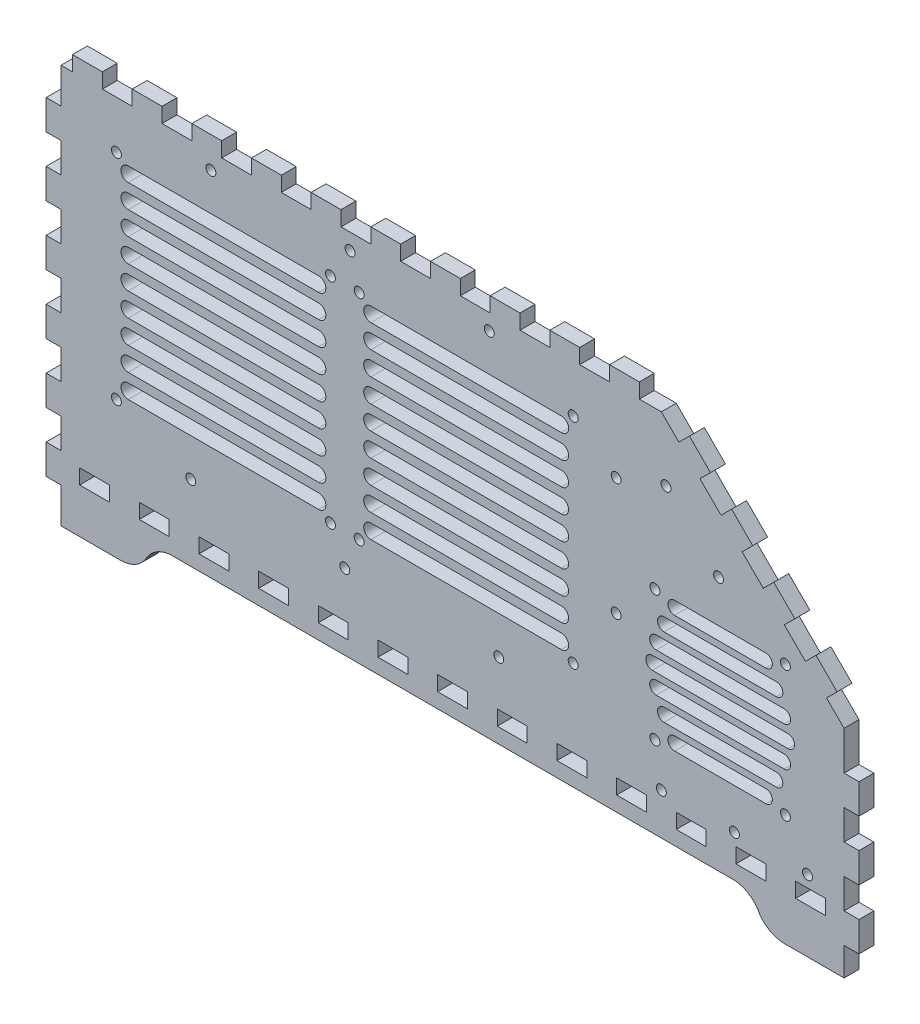
SolidWorks part; units mm, degrees
ref_plane "Front Plane" through (0, 0, 0) normal (0, 0, 1) x (1, 0, 0)
ref_plane "Top Plane" through (0, 0, 0) normal (0, 1, 0) x (1, 0, 0)
ref_plane "Right Plane" through (0, 0, 0) normal (1, 0, 0) x (0, 0, -1)
sketch "Model" plane through (0, 0, 0) normal (0, 0, 1) x (1, 0, 0)
  line L4 (28.9553, 40.0032) -> (23.2406, 40.0032)
  line L5 (23.2406, 40.0032) -> (23.2406, 45.7179)
  line L6 (23.2406, 45.7179) -> (34.67, 45.7179)
  line L7 (34.67, 45.7179) -> (34.67, 40.0032)
  line L8 (34.67, 40.0032) -> (28.9553, 40.0032)
  line L9 (51.8156, 40.0032) -> (46.0996, 40.0032)
  line L10 (46.0996, 40.0032) -> (46.0996, 45.7179)
  line L11 (46.0996, 45.7179) -> (57.5303, 45.7179)
  line L12 (57.5303, 45.7179) -> (57.5303, 40.0032)
  line L13 (57.5303, 40.0032) -> (51.8156, 40.0032)
  line L14 (74.6746, 40.0032) -> (68.9599, 40.0032)
  line L15 (68.9599, 40.0032) -> (68.9599, 45.7179)
  line L16 (68.9599, 45.7179) -> (80.3906, 45.7179)
  line L17 (80.3906, 45.7179) -> (80.3906, 40.0032)
  line L18 (80.3906, 40.0032) -> (74.6746, 40.0032)
  line L19 (97.5349, 40.0032) -> (91.8199, 40.0032)
  line L20 (91.8199, 40.0032) -> (91.8199, 45.7179)
  line L21 (91.8199, 45.7179) -> (103.25, 45.7179)
  line L22 (103.25, 45.7179) -> (103.25, 40.0032)
  line L23 (103.25, 40.0032) -> (97.5349, 40.0032)
  line L24 (120.395, 40.0032) -> (114.68, 40.0032)
  line L25 (114.68, 40.0032) -> (114.68, 45.7179)
  line L26 (114.68, 45.7179) -> (126.11, 45.7179)
  line L27 (126.11, 45.7179) -> (126.11, 40.0032)
  line L28 (126.11, 40.0032) -> (120.395, 40.0032)
  line L29 (143.255, 40.0032) -> (137.541, 40.0032)
  line L30 (137.541, 40.0032) -> (137.541, 45.7179)
  line L31 (137.541, 45.7179) -> (148.97, 45.7179)
  line L32 (148.97, 45.7179) -> (148.97, 40.0032)
  line L33 (148.97, 40.0032) -> (143.255, 40.0032)
  line L34 (166.116, 40.0032) -> (160.4, 40.0032)
  line L35 (160.4, 40.0032) -> (160.4, 45.7179)
  line L36 (160.4, 45.7179) -> (171.83, 45.7179)
  line L37 (171.83, 45.7179) -> (171.83, 40.0032)
  line L38 (171.83, 40.0032) -> (166.116, 40.0032)
  line L39 (188.975, 40.0032) -> (183.26, 40.0032)
  line L40 (183.26, 40.0032) -> (183.26, 45.7179)
  line L41 (183.26, 45.7179) -> (194.691, 45.7179)
  line L42 (194.691, 45.7179) -> (194.691, 40.0032)
  line L43 (194.691, 40.0032) -> (188.975, 40.0032)
  line L44 (211.835, 40.0032) -> (206.12, 40.0032)
  line L45 (206.12, 40.0032) -> (206.12, 45.7179)
  line L46 (206.12, 45.7179) -> (217.55, 45.7179)
  line L47 (217.55, 45.7179) -> (217.55, 40.0032)
  line L48 (217.55, 40.0032) -> (211.835, 40.0032)
  line L49 (234.695, 40.0032) -> (228.98, 40.0032)
  line L50 (228.98, 40.0032) -> (228.98, 45.7179)
  line L51 (228.98, 45.7179) -> (240.41, 45.7179)
  line L52 (240.41, 45.7179) -> (240.41, 40.0032)
  line L53 (240.41, 40.0032) -> (234.695, 40.0032)
  line L54 (257.555, 40.0032) -> (251.841, 40.0032)
  line L55 (251.841, 40.0032) -> (251.841, 45.7179)
  line L56 (251.841, 45.7179) -> (263.27, 45.7179)
  line L57 (263.27, 45.7179) -> (263.27, 40.0032)
  line L58 (263.27, 40.0032) -> (257.555, 40.0032)
  line L59 (280.416, 40.0032) -> (274.7, 40.0032)
  line L60 (274.7, 40.0032) -> (274.7, 45.7179)
  line L61 (274.7, 45.7179) -> (286.13, 45.7179)
  line L62 (286.13, 45.7179) -> (286.13, 40.0032)
  line L63 (286.13, 40.0032) -> (280.416, 40.0032)
  line L64 (303.275, 40.0032) -> (297.56, 40.0032)
  line L65 (297.56, 40.0032) -> (297.56, 45.7179)
  line L66 (297.56, 45.7179) -> (308.991, 45.7179)
  line L67 (308.991, 45.7179) -> (308.991, 40.0032)
  line L68 (308.991, 40.0032) -> (303.275, 40.0032)
  line L69 (16.1148, 22.8575) -> (38.9749, 22.8575)
  line L70 (38.9749, 22.8575) -> (39.3485, 22.8575)
  line L71 (39.3485, 22.8575) -> (40.4689, 22.9567)
  line L72 (40.4689, 22.9567) -> (41.9322, 23.2475)
  line L73 (41.9322, 23.2475) -> (43.3447, 23.7271)
  line L74 (43.3447, 23.7271) -> (44.366, 24.2025)
  line L75 (44.366, 24.2025) -> (44.6899, 24.3885)
  line L76 (44.6899, 24.3885) -> (44.8511, 24.4822)
  line L77 (44.8511, 24.4822) -> (45.3263, 24.7854)
  line L78 (45.3263, 24.7854) -> (45.9341, 25.2222)
  line L79 (45.9341, 25.2222) -> (46.5116, 25.6963)
  line L80 (46.5116, 25.6963) -> (47.056, 26.2062)
  line L81 (47.056, 26.2062) -> (47.5657, 26.7505)
  line L82 (47.5657, 26.7505) -> (48.0399, 27.3279)
  line L83 (48.0399, 27.3279) -> (48.4766, 27.9356)
  line L84 (48.4766, 27.9356) -> (48.7796, 28.411)
  line L85 (48.7796, 28.411) -> (48.8735, 28.5722)
  line L86 (48.8735, 28.5722) -> (48.9673, 28.7348)
  line L87 (48.9673, 28.7348) -> (49.2689, 29.2103)
  line L88 (49.2689, 29.2103) -> (49.7057, 29.818)
  line L89 (49.7057, 29.818) -> (50.1798, 30.3954)
  line L90 (50.1798, 30.3954) -> (50.6899, 30.9397)
  line L91 (50.6899, 30.9397) -> (51.2339, 31.4496)
  line L92 (51.2339, 31.4496) -> (51.8114, 31.9236)
  line L93 (51.8114, 31.9236) -> (52.4192, 32.3605)
  line L94 (52.4192, 32.3605) -> (52.8948, 32.6622)
  line L95 (52.8948, 32.6622) -> (53.0571, 32.756)
  line L96 (53.0571, 32.756) -> (53.3799, 32.9434)
  line L97 (53.3799, 32.9434) -> (54.4008, 33.4188)
  line L98 (54.4008, 33.4188) -> (55.8133, 33.8983)
  line L99 (55.8133, 33.8983) -> (57.2766, 34.1891)
  line L100 (57.2766, 34.1891) -> (58.3971, 34.287)
  line L101 (58.3971, 34.287) -> (58.7721, 34.287)
  line L102 (58.7721, 34.287) -> (273.458, 34.287)
  line L103 (273.458, 34.287) -> (273.831, 34.287)
  line L104 (273.831, 34.287) -> (274.952, 34.1891)
  line L105 (274.952, 34.1891) -> (276.415, 33.8983)
  line L106 (276.415, 33.8983) -> (277.828, 33.4188)
  line L107 (277.828, 33.4188) -> (278.849, 32.9434)
  line L108 (278.849, 32.9434) -> (279.172, 32.756)
  line L109 (279.172, 32.756) -> (279.334, 32.6636)
  line L110 (279.334, 32.6636) -> (279.809, 32.3605)
  line L111 (279.809, 32.3605) -> (280.417, 31.9236)
  line L112 (280.417, 31.9236) -> (280.995, 31.4496)
  line L113 (280.995, 31.4496) -> (281.539, 30.9397)
  line L114 (281.539, 30.9397) -> (282.049, 30.3954)
  line L115 (282.049, 30.3954) -> (282.523, 29.818)
  line L116 (282.523, 29.818) -> (282.96, 29.2103)
  line L117 (282.96, 29.2103) -> (283.263, 28.7348)
  line L118 (283.263, 28.7348) -> (283.356, 28.5722)
  line L119 (283.356, 28.5722) -> (283.449, 28.411)
  line L120 (283.449, 28.411) -> (283.752, 27.9356)
  line L121 (283.752, 27.9356) -> (284.189, 27.3279)
  line L122 (284.189, 27.3279) -> (284.663, 26.7505)
  line L123 (284.663, 26.7505) -> (285.172, 26.2062)
  line L124 (285.172, 26.2062) -> (285.717, 25.6963)
  line L125 (285.717, 25.6963) -> (286.294, 25.2222)
  line L126 (286.294, 25.2222) -> (286.902, 24.7854)
  line L127 (286.902, 24.7854) -> (287.377, 24.4822)
  line L128 (287.377, 24.4822) -> (287.54, 24.3885)
  line L129 (287.54, 24.3885) -> (287.862, 24.2025)
  line L130 (287.862, 24.2025) -> (288.884, 23.7271)
  line L131 (288.884, 23.7271) -> (290.296, 23.2475)
  line L132 (290.296, 23.2475) -> (291.76, 22.9567)
  line L133 (291.76, 22.9567) -> (292.88, 22.8575)
  line L134 (292.88, 22.8575) -> (293.255, 22.8575)
  line L135 (293.255, 22.8575) -> (316.115, 22.8575)
  line L136 (316.115, 22.8575) -> (316.115, 33.6917)
  line L137 (316.115, 33.6917) -> (321.83, 33.6917)
  line L138 (321.83, 33.6917) -> (321.83, 45.1224)
  line L139 (321.83, 45.1224) -> (316.115, 45.1224)
  line L140 (316.115, 45.1224) -> (316.115, 56.552)
  line L141 (316.115, 56.552) -> (321.83, 56.552)
  line L142 (321.83, 56.552) -> (321.83, 67.9813)
  line L143 (321.83, 67.9813) -> (316.115, 67.9813)
  line L144 (316.115, 67.9813) -> (316.115, 79.412)
  line L145 (316.115, 79.412) -> (321.83, 79.412)
  line L146 (321.83, 79.412) -> (321.83, 90.8417)
  line L147 (321.83, 90.8417) -> (316.115, 90.8417)
  line L148 (316.115, 90.8417) -> (316.115, 101.677)
  line L149 (316.115, 101.677) -> (316.115, 105.718)
  line L150 (316.115, 105.718) -> (309.403, 112.43)
  line L151 (309.403, 112.43) -> (313.444, 116.47)
  line L152 (313.444, 116.47) -> (305.362, 124.553)
  line L153 (305.362, 124.553) -> (301.321, 120.512)
  line L154 (301.321, 120.512) -> (293.238, 128.595)
  line L155 (293.238, 128.595) -> (297.28, 132.635)
  line L156 (297.28, 132.635) -> (289.198, 140.717)
  line L157 (289.198, 140.717) -> (285.156, 136.677)
  line L158 (285.156, 136.677) -> (277.074, 144.759)
  line L159 (277.074, 144.759) -> (281.114, 148.801)
  line L160 (281.114, 148.801) -> (273.032, 156.881)
  line L161 (273.032, 156.881) -> (268.992, 152.841)
  line L162 (268.992, 152.841) -> (260.91, 160.923)
  line L163 (260.91, 160.923) -> (264.951, 164.963)
  line L164 (264.951, 164.963) -> (256.869, 173.046)
  line L165 (256.869, 173.046) -> (252.827, 169.005)
  line L166 (252.827, 169.005) -> (246.115, 175.718)
  line L167 (246.115, 175.718) -> (242.074, 175.718)
  line L168 (242.074, 175.718) -> (237.68, 175.718)
  line L169 (237.68, 175.718) -> (237.68, 181.433)
  line L170 (237.68, 181.433) -> (226.249, 181.433)
  line L171 (226.249, 181.433) -> (226.249, 175.718)
  line L172 (226.249, 175.718) -> (214.82, 175.718)
  line L173 (214.82, 175.718) -> (214.82, 181.433)
  line L174 (214.82, 181.433) -> (203.389, 181.433)
  line L175 (203.389, 181.433) -> (203.389, 175.718)
  line L176 (203.389, 175.718) -> (191.959, 175.718)
  line L177 (191.959, 175.718) -> (191.959, 181.433)
  line L178 (191.959, 181.433) -> (180.53, 181.433)
  line L179 (180.53, 181.433) -> (180.53, 175.718)
  line L180 (180.53, 175.718) -> (169.099, 175.718)
  line L181 (169.099, 175.718) -> (169.099, 181.433)
  line L182 (169.099, 181.433) -> (157.67, 181.433)
  line L183 (157.67, 181.433) -> (157.67, 175.718)
  line L184 (157.67, 175.718) -> (146.239, 175.718)
  line L185 (146.239, 175.718) -> (146.239, 181.433)
  line L186 (146.239, 181.433) -> (134.809, 181.433)
  line L187 (134.809, 181.433) -> (134.809, 175.718)
  line L188 (134.809, 175.718) -> (123.38, 175.718)
  line L189 (123.38, 175.718) -> (123.38, 181.433)
  line L190 (123.38, 181.433) -> (111.949, 181.433)
  line L191 (111.949, 181.433) -> (111.949, 175.718)
  line L192 (111.949, 175.718) -> (100.52, 175.718)
  line L193 (100.52, 175.718) -> (100.52, 181.433)
  line L194 (100.52, 181.433) -> (89.0887, 181.433)
  line L195 (89.0887, 181.433) -> (89.0887, 175.718)
  line L196 (89.0887, 175.718) -> (77.6594, 175.718)
  line L197 (77.6594, 175.718) -> (77.6594, 181.433)
  line L198 (77.6594, 181.433) -> (66.2298, 181.433)
  line L199 (66.2298, 181.433) -> (66.2298, 175.718)
  line L200 (66.2298, 175.718) -> (54.7991, 175.718)
  line L201 (54.7991, 175.718) -> (54.7991, 181.433)
  line L202 (54.7991, 181.433) -> (43.3698, 181.433)
  line L203 (43.3698, 181.433) -> (43.3698, 175.718)
  line L204 (43.3698, 175.718) -> (31.9388, 175.718)
  line L205 (31.9388, 175.718) -> (31.9388, 181.433)
  line L206 (31.9388, 181.433) -> (20.5093, 181.433)
  line L207 (20.5093, 181.433) -> (20.5093, 175.718)
  line L208 (20.5093, 175.718) -> (16.1148, 175.718)
  line L209 (16.1148, 175.718) -> (16.1148, 162.153)
  line L210 (16.1148, 162.153) -> (10.4001, 162.153)
  line L211 (10.4001, 162.153) -> (10.4001, 150.723)
  line L212 (10.4001, 150.723) -> (16.1148, 150.723)
  line L213 (16.1148, 150.723) -> (16.1148, 139.292)
  line L214 (16.1148, 139.292) -> (10.4001, 139.292)
  line L215 (10.4001, 139.292) -> (10.4001, 127.863)
  line L216 (10.4001, 127.863) -> (16.1148, 127.863)
  line L217 (16.1148, 127.863) -> (16.1148, 116.433)
  line L218 (16.1148, 116.433) -> (10.4001, 116.433)
  line L219 (10.4001, 116.433) -> (10.4001, 105.003)
  line L220 (10.4001, 105.003) -> (16.1148, 105.003)
  line L221 (16.1148, 105.003) -> (16.1148, 93.5729)
  line L222 (16.1148, 93.5729) -> (10.4001, 93.5729)
  line L223 (10.4001, 93.5729) -> (10.4001, 82.1422)
  line L224 (10.4001, 82.1422) -> (16.1148, 82.1422)
  line L225 (16.1148, 82.1422) -> (16.1148, 70.7125)
  line L226 (16.1148, 70.7125) -> (10.4001, 70.7125)
  line L227 (10.4001, 70.7125) -> (10.4001, 59.2832)
  line L228 (10.4001, 59.2832) -> (16.1148, 59.2832)
  line L229 (16.1148, 59.2832) -> (16.1148, 47.8525)
  line L230 (16.1148, 47.8525) -> (10.4001, 47.8525)
  line L231 (10.4001, 47.8525) -> (10.4001, 36.4229)
  line L232 (10.4001, 36.4229) -> (16.1148, 36.4229)
  line L233 (16.1148, 36.4229) -> (16.1148, 22.8575)
extrude "Boss-Extrude1" add sketch "Model" along normal blind 5.715
sketch "Sketch1" plane through (0, 0, 0) normal (0, 0, -1) x (-1, 0, 0)
  line L0 (-268.6476, 115.7127) -> (-268.6476, 65.7127) construction
  line L1 (-293.6476, 115.7127) -> (-243.6476, 115.7127) construction
  line L2 (-293.6476, 115.7127) -> (-293.6476, 65.7127) construction
  line L3 (-293.6476, 65.7127) -> (-243.6476, 65.7127) construction
  line L4 (-243.6476, 115.7127) -> (-243.6476, 65.7127) construction
  line L5 (-286.1476, 113.2127) -> (-251.1476, 113.2127) construction
  line L6 (-286.1476, 115.7127) -> (-251.1476, 115.7127)
  line L7 (-286.1476, 110.7127) -> (-251.1476, 110.7127)
  line L8 (-290.1476, 103.2127) -> (-247.1476, 103.2127)
  line L9 (-290.1476, 108.2127) -> (-247.1476, 108.2127)
  line L10 (-290.1476, 105.7127) -> (-247.1476, 105.7127) construction
  line L11 (-293.1476, 95.7127) -> (-244.1476, 95.7127)
  line L12 (-293.1476, 100.7127) -> (-244.1476, 100.7127)
  line L13 (-293.1476, 98.2127) -> (-244.1476, 98.2127) construction
  line L14 (-294.6476, 88.2127) -> (-242.6476, 88.2127)
  line L15 (-294.6476, 93.2127) -> (-242.6476, 93.2127)
  line L16 (-294.6476, 90.7127) -> (-242.6476, 90.7127) construction
  line L17 (-293.1476, 80.7127) -> (-244.1476, 80.7127)
  line L18 (-293.1476, 85.7127) -> (-244.1476, 85.7127)
  line L19 (-293.1476, 83.2127) -> (-244.1476, 83.2127) construction
  line L20 (-290.1476, 73.2127) -> (-247.1476, 73.2127)
  line L21 (-290.1476, 78.2127) -> (-247.1476, 78.2127)
  line L22 (-290.1476, 75.7127) -> (-247.1476, 75.7127) construction
  line L23 (-286.1476, 65.7127) -> (-251.1476, 65.7127)
  line L24 (-286.1476, 70.7127) -> (-251.1476, 70.7127)
  line L25 (-286.1476, 68.2127) -> (-251.1476, 68.2127) construction
  line L26 (-279.0487, 113.2127) -> (-279.0487, 105.7127) construction
  line L27 (-279.0487, 105.7127) -> (-279.0487, 98.2127) construction
  line L28 (-279.0487, 98.2127) -> (-279.0487, 90.7127) construction
  line L29 (-279.0487, 90.7127) -> (-279.0487, 83.2127) construction
  line L30 (-279.0487, 83.2127) -> (-279.0487, 75.7127) construction
  arc A0 (-286.1476, 115.7127) -> (-286.1476, 110.7127) centre (-286.1476, 113.2127) ccw
  arc A1 (-251.1476, 110.7127) -> (-251.1476, 115.7127) centre (-251.1476, 113.2127) ccw
  arc A2 (-290.1476, 108.2127) -> (-290.1476, 103.2127) centre (-290.1476, 105.7127) ccw
  arc A3 (-247.1476, 103.2127) -> (-247.1476, 108.2127) centre (-247.1476, 105.7127) ccw
  arc A4 (-293.1476, 100.7127) -> (-293.1476, 95.7127) centre (-293.1476, 98.2127) ccw
  arc A5 (-244.1476, 95.7127) -> (-244.1476, 100.7127) centre (-244.1476, 98.2127) ccw
  arc A6 (-294.6476, 93.2127) -> (-294.6476, 88.2127) centre (-294.6476, 90.7127) ccw
  arc A7 (-242.6476, 88.2127) -> (-242.6476, 93.2127) centre (-242.6476, 90.7127) ccw
  arc A8 (-293.1476, 85.7127) -> (-293.1476, 80.7127) centre (-293.1476, 83.2127) ccw
  arc A9 (-244.1476, 80.7127) -> (-244.1476, 85.7127) centre (-244.1476, 83.2127) ccw
  arc A10 (-290.1476, 78.2127) -> (-290.1476, 73.2127) centre (-290.1476, 75.7127) ccw
  arc A11 (-247.1476, 73.2127) -> (-247.1476, 78.2127) centre (-247.1476, 75.7127) ccw
  arc A12 (-286.1476, 70.7127) -> (-286.1476, 65.7127) centre (-286.1476, 68.2127) ccw
  arc A13 (-251.1476, 65.7127) -> (-251.1476, 70.7127) centre (-251.1476, 68.2127) ccw
  point P10 (-268.6476, 113.2127)
  point P18 (-268.6476, 105.7127)
  point P25 (-268.6476, 98.2127)
  point P32 (-268.6476, 90.7127)
  point P39 (-268.6476, 83.2127)
  point P46 (-268.6476, 75.7127)
  point P53 (-268.6476, 68.2127)
  dimension "D3" = 2.5
  dimension "D1" = 35
  dimension "D2" = 2.5
  dimension "D4" = 2.5
  dimension "D7" = 43
  dimension "D9" = 49
  dimension "D13" = 52
extrude "Cut-Extrude1" cut sketch "Sketch1" against normal through all
hole_wizard "#6 Clearance Hole2" positions "Sketch2" profile "Sketch3" hole size "#6" standard "ANSI Inch" end condition through all
sketch "Sketch2" plane through (0, 0, 0) normal (0, 0, -1) x (-1, 0, 0)
  point P0 (-293.6476, 115.7127)
  point P3 (-243.6476, 115.7127)
  point P6 (-293.6476, 65.7127)
  point P9 (-243.6476, 65.7127)
sketch "Sketch3" plane through (293.6476, 115.7127, 0) normal (1, 0, 0) x (0, 1, 0)
  line L0 (0, 0) -> (0, 5.715)
  line L1 (0, 5.715) -> (1.8986, 5.715)
  line L2 (1.8986, 5.715) -> (1.8986, 0)
  line L5 (1.8986, 0) -> (0, 0)
  line L11 (0, -6.35) -> (0, 107.95) construction
  dimension "Thru Hole Dia." = 3.7973
  dimension "Thru Hole Depth" = 5.715
sketch "Sketch4" plane through (0, 0, 0) normal (0, 0, -1) x (-1, 0, 0)
  line L0 (-37.3313, 75.4325) -> (-212.3313, 75.4325) construction
  line L1 (-212.3313, 75.4325) -> (-212.3313, 157.4325) construction
  line L2 (-212.3313, 157.4325) -> (-130.3313, 157.4325) construction
  line L3 (-37.3314, 157.4325) -> (-37.3313, 75.4325) construction
  line L4 (-130.3313, 157.4325) -> (-130.3313, 75.4325) construction
  line L5 (-119.3313, 157.4325) -> (-119.3313, 75.4325) construction
  line L6 (-130.3313, 157.4325) -> (-119.3313, 157.4325) construction
  line L7 (-119.3313, 157.4325) -> (-37.3314, 157.4325) construction
  line L8 (-171.3313, 157.4325) -> (-171.3313, 75.4325) construction
  line L9 (-124.8313, 157.4325) -> (-124.8313, 75.4325) construction
  line L10 (-207.8313, 152.4325) -> (-134.8313, 152.4325) construction
  line L11 (-207.8313, 155.1825) -> (-134.8313, 155.1825)
  line L12 (-207.8313, 149.6825) -> (-134.8313, 149.6825)
  line L13 (-207.8313, 140.6825) -> (-134.8313, 140.6825)
  line L14 (-207.8313, 146.1825) -> (-134.8313, 146.1825)
  line L15 (-207.8313, 143.4325) -> (-134.8313, 143.4325) construction
  line L16 (-207.8313, 131.6825) -> (-134.8313, 131.6825)
  line L17 (-207.8313, 137.1825) -> (-134.8313, 137.1825)
  line L18 (-207.8313, 134.4325) -> (-134.8313, 134.4325) construction
  line L19 (-207.8313, 122.6825) -> (-134.8313, 122.6825)
  line L20 (-207.8313, 128.1825) -> (-134.8313, 128.1825)
  line L21 (-207.8313, 125.4325) -> (-134.8313, 125.4325) construction
  line L22 (-207.8313, 113.6825) -> (-134.8313, 113.6825)
  line L23 (-207.8313, 119.1825) -> (-134.8313, 119.1825)
  line L24 (-207.8313, 116.4325) -> (-134.8313, 116.4325) construction
  line L25 (-207.8313, 104.6825) -> (-134.8313, 104.6825)
  line L26 (-207.8313, 110.1825) -> (-134.8313, 110.1825)
  line L27 (-207.8313, 107.4325) -> (-134.8313, 107.4325) construction
  line L28 (-207.8313, 95.6825) -> (-134.8313, 95.6825)
  line L29 (-207.8313, 101.1825) -> (-134.8313, 101.1825)
  line L30 (-207.8313, 98.4325) -> (-134.8313, 98.4325) construction
  line L31 (-207.8313, 86.6825) -> (-134.8313, 86.6825)
  line L32 (-207.8313, 92.1825) -> (-134.8313, 92.1825)
  line L33 (-207.8313, 89.4325) -> (-134.8313, 89.4325) construction
  line L34 (-207.8313, 77.6825) -> (-134.8313, 77.6825)
  line L35 (-207.8313, 83.1825) -> (-134.8313, 83.1825)
  line L36 (-207.8313, 80.4325) -> (-134.8313, 80.4325) construction
  line L37 (-41.8314, 80.4325) -> (-114.8314, 80.4325) construction
  line L38 (-41.8314, 83.1825) -> (-114.8314, 83.1825)
  line L39 (-41.8314, 77.6825) -> (-114.8314, 77.6825)
  line L40 (-41.8314, 89.4325) -> (-114.8314, 89.4325) construction
  line L41 (-41.8314, 92.1825) -> (-114.8314, 92.1825)
  line L42 (-41.8314, 86.6825) -> (-114.8314, 86.6825)
  line L43 (-41.8314, 98.4325) -> (-114.8314, 98.4325) construction
  line L44 (-41.8314, 101.1825) -> (-114.8314, 101.1825)
  line L45 (-41.8314, 95.6825) -> (-114.8314, 95.6825)
  line L46 (-41.8314, 107.4325) -> (-114.8314, 107.4325) construction
  line L47 (-41.8314, 110.1825) -> (-114.8314, 110.1825)
  line L48 (-41.8314, 104.6825) -> (-114.8314, 104.6825)
  line L49 (-41.8314, 116.4325) -> (-114.8314, 116.4325) construction
  line L50 (-41.8314, 119.1825) -> (-114.8314, 119.1825)
  line L51 (-41.8314, 113.6825) -> (-114.8314, 113.6825)
  line L52 (-41.8314, 125.4325) -> (-114.8314, 125.4325) construction
  line L53 (-41.8314, 128.1825) -> (-114.8314, 128.1825)
  line L54 (-41.8314, 122.6825) -> (-114.8314, 122.6825)
  line L55 (-41.8314, 134.4325) -> (-114.8314, 134.4325) construction
  line L56 (-41.8314, 137.1825) -> (-114.8314, 137.1825)
  line L57 (-41.8314, 131.6825) -> (-114.8314, 131.6825)
  line L58 (-41.8314, 143.4325) -> (-114.8314, 143.4325) construction
  line L59 (-41.8314, 146.1825) -> (-114.8314, 146.1825)
  line L60 (-41.8314, 140.6825) -> (-114.8314, 140.6825)
  line L61 (-41.8314, 152.4325) -> (-114.8314, 152.4325) construction
  line L62 (-41.8314, 155.1825) -> (-114.8313, 155.1825)
  line L63 (-41.8314, 149.6825) -> (-114.8313, 149.6825)
  arc A0 (-207.8313, 155.1825) -> (-207.8313, 149.6825) centre (-207.8313, 152.4325) ccw
  arc A1 (-134.8313, 149.6825) -> (-134.8313, 155.1825) centre (-134.8313, 152.4325) ccw
  arc A2 (-207.8313, 146.1825) -> (-207.8313, 140.6825) centre (-207.8313, 143.4325) ccw
  arc A3 (-134.8313, 140.6825) -> (-134.8313, 146.1825) centre (-134.8313, 143.4325) ccw
  arc A4 (-207.8313, 137.1825) -> (-207.8313, 131.6825) centre (-207.8313, 134.4325) ccw
  arc A5 (-134.8313, 131.6825) -> (-134.8313, 137.1825) centre (-134.8313, 134.4325) ccw
  arc A6 (-207.8313, 128.1825) -> (-207.8313, 122.6825) centre (-207.8313, 125.4325) ccw
  arc A7 (-134.8313, 122.6825) -> (-134.8313, 128.1825) centre (-134.8313, 125.4325) ccw
  arc A8 (-207.8313, 119.1825) -> (-207.8313, 113.6825) centre (-207.8313, 116.4325) ccw
  arc A9 (-134.8313, 113.6825) -> (-134.8313, 119.1825) centre (-134.8313, 116.4325) ccw
  arc A10 (-207.8313, 110.1825) -> (-207.8313, 104.6825) centre (-207.8313, 107.4325) ccw
  arc A11 (-134.8313, 104.6825) -> (-134.8313, 110.1825) centre (-134.8313, 107.4325) ccw
  arc A12 (-207.8313, 101.1825) -> (-207.8313, 95.6825) centre (-207.8313, 98.4325) ccw
  arc A13 (-134.8313, 95.6825) -> (-134.8313, 101.1825) centre (-134.8313, 98.4325) ccw
  arc A14 (-207.8313, 92.1825) -> (-207.8313, 86.6825) centre (-207.8313, 89.4325) ccw
  arc A15 (-134.8313, 86.6825) -> (-134.8313, 92.1825) centre (-134.8313, 89.4325) ccw
  arc A16 (-207.8313, 83.1825) -> (-207.8313, 77.6825) centre (-207.8313, 80.4325) ccw
  arc A17 (-134.8313, 77.6825) -> (-134.8313, 83.1825) centre (-134.8313, 80.4325) ccw
  arc A18 (-41.8314, 83.1825) -> (-41.8314, 77.6825) centre (-41.8314, 80.4325) cw
  arc A19 (-114.8314, 77.6825) -> (-114.8314, 83.1825) centre (-114.8314, 80.4325) cw
  arc A20 (-41.8314, 92.1825) -> (-41.8314, 86.6825) centre (-41.8314, 89.4325) cw
  arc A21 (-114.8314, 86.6825) -> (-114.8314, 92.1825) centre (-114.8314, 89.4325) cw
  arc A22 (-41.8314, 101.1825) -> (-41.8314, 95.6825) centre (-41.8314, 98.4325) cw
  arc A23 (-114.8314, 95.6825) -> (-114.8314, 101.1825) centre (-114.8314, 98.4325) cw
  arc A24 (-41.8314, 110.1825) -> (-41.8314, 104.6825) centre (-41.8314, 107.4325) cw
  arc A25 (-114.8314, 104.6825) -> (-114.8314, 110.1825) centre (-114.8314, 107.4325) cw
  arc A26 (-41.8314, 119.1825) -> (-41.8314, 113.6825) centre (-41.8314, 116.4325) cw
  arc A27 (-114.8314, 113.6825) -> (-114.8314, 119.1825) centre (-114.8314, 116.4325) cw
  arc A28 (-41.8314, 128.1825) -> (-41.8314, 122.6825) centre (-41.8314, 125.4325) cw
  arc A29 (-114.8314, 122.6825) -> (-114.8314, 128.1825) centre (-114.8314, 125.4325) cw
  arc A30 (-41.8314, 137.1825) -> (-41.8314, 131.6825) centre (-41.8314, 134.4325) cw
  arc A31 (-114.8314, 131.6825) -> (-114.8314, 137.1825) centre (-114.8314, 134.4325) cw
  arc A32 (-41.8314, 146.1825) -> (-41.8314, 140.6825) centre (-41.8314, 143.4325) cw
  arc A33 (-114.8314, 140.6825) -> (-114.8314, 146.1825) centre (-114.8314, 143.4325) cw
  arc A34 (-41.8314, 155.1825) -> (-41.8314, 149.6825) centre (-41.8314, 152.4325) cw
  arc A35 (-114.8313, 149.6825) -> (-114.8313, 155.1825) centre (-114.8314, 152.4325) cw
  point P3 (-37.3314, 157.4325)
  point P4 (-130.3313, 157.4325)
  point P9 (-119.3313, 157.4325)
  point P11 (-130.3313, 75.4325)
  point P13 (-119.3313, 75.4325)
  point P26 (-171.3313, 152.4325)
  point P35 (-171.3313, 143.4325)
  point P42 (-171.3313, 134.4325)
  point P49 (-171.3313, 125.4325)
  point P56 (-171.3313, 116.4325)
  point P63 (-171.3313, 107.4325)
  point P70 (-171.3313, 98.4325)
  point P77 (-171.3313, 89.4325)
  point P84 (-171.3313, 80.4325)
  point P89 (-78.3314, 80.4325)
  point P96 (-78.3314, 89.4325)
  point P103 (-78.3314, 98.4325)
  point P110 (-78.3314, 107.4325)
  point P117 (-78.3314, 116.4325)
  point P124 (-78.3314, 125.4325)
  point P131 (-78.3314, 134.4325)
  point P138 (-78.3314, 143.4325)
  point P145 (-78.3314, 152.4325)
  dimension "D2" = 2.75
  dimension "D1" = 73
  dimension "D3" = 5
  dimension "D5" = 9
  dimension "D6" = 82
  dimension "D7" = 175
  dimension "D8" = 11
  dimension "D4" = 9
extrude "Cut-Extrude2" cut sketch "Sketch4" against normal blind 10
hole_wizard "#6 Clearance Hole1" positions "Sketch5" profile "Sketch6" hole size "#6" standard "ANSI Inch" end condition through all
sketch "Sketch5" plane through (0, 0, 0) normal (0, 0, -1) x (-1, 0, 0)
  point P0 (-212.3313, 157.4325)
  point P3 (-130.3313, 157.4325)
  point P6 (-119.3313, 157.4325)
  point P9 (-37.3314, 157.4325)
  point P12 (-37.3313, 75.4325)
  point P15 (-119.3313, 75.4325)
  point P18 (-130.3314, 75.4325)
  point P21 (-212.3313, 75.4325)
sketch "Sketch6" plane through (212.3313, 157.4325, 0) normal (1, 0, 0) x (0, 1, 0)
  line L0 (0, 0) -> (0, 5.715)
  line L1 (0, 5.715) -> (1.8986, 5.715)
  line L2 (1.8986, 5.715) -> (1.8986, 0)
  line L5 (1.8986, 0) -> (0, 0)
  line L11 (0, -6.35) -> (0, 107.95) construction
  dimension "Thru Hole Dia." = 3.7973
  dimension "Thru Hole Depth" = 5.715
sketch "Sketch7" plane through (0, 0, 0) normal (0, 0, -1) x (-1, 0, 0)
  point P0 (-180.1984, 169.575)
  point P1 (-126.8651, 169.575)
  point P3 (-73.5318, 169.575)
sketch "Sketch10" plane through (0, 0, 0) normal (0, 0, -1) x (-1, 0, 0)
  point P0 (-183.8313, 63.2127)
  point P1 (-124.8313, 63.2127)
  point P3 (-65.8313, 63.2127)
  point P5 (-228.7976, 145.2151)
  point P7 (-228.7976, 100.2151)
  point P9 (-247.8954, 152.0078)
  point P11 (-268.048, 131.8553)
  point P13 (-311.6141, 79.7127)
  point P15 (-274.1141, 50.2127)
  point P17 (-246.1141, 50.2127)
  point P19 (-302.1141, 50.2127)
hole_wizard "#6 Clearance Hole3" positions "Sketch8" profile "Sketch9" hole size "#6" standard "ANSI Inch" end condition through all
sketch "Sketch8" plane through (0, 0, 5.715) normal (0, 0, 1) x (1, 0, 0)
  point P0 (73.5318, 169.575)
  point P3 (126.8651, 169.575)
  point P6 (180.1984, 169.575)
  point P9 (65.8313, 63.2127)
  point P12 (183.8313, 63.2127)
  point P15 (124.8313, 63.2127)
  point P19 (228.7976, 145.2151)
  point P22 (228.7976, 100.2151)
  point P26 (246.1141, 50.2127)
  point P29 (274.1141, 50.2127)
  point P32 (302.1141, 50.2127)
  point P35 (268.048, 131.8553)
  point P38 (247.8954, 152.0078)
sketch "Sketch9" plane through (73.5318, 169.575, 5.715) normal (1, 0, 0) x (0, -1, 0)
  line L0 (0, 0) -> (0, 5.715)
  line L1 (0, 5.715) -> (1.8986, 5.715)
  line L2 (1.8986, 5.715) -> (1.8986, 0)
  line L5 (1.8986, 0) -> (0, 0)
  line L11 (0, -6.35) -> (0, 107.95) construction
  dimension "Thru Hole Dia." = 3.7973
  dimension "Thru Hole Depth" = 5.715
